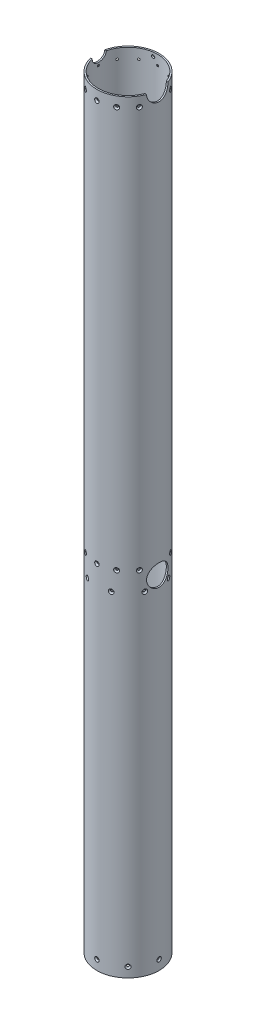
SolidWorks part; units mm, degrees
material "6063-T6"
ref_plane "Front Plane" through (0, 0, 0) normal (0, 0, 1) x (1, 0, 0)
ref_plane "Top Plane" through (0, 0, 0) normal (0, 1, 0) x (1, 0, 0)
ref_plane "Right Plane" through (0, 0, 0) normal (1, 0, 0) x (0, 0, -1)
sketch "Sketch1" plane through (0, 0, 0) normal (0, 1, 0) x (1, 0, 0)
  circle A0 centre (0, 0) radius 24.1554
  circle A1 centre (0, 0) radius 25.4
  dimension "D1" = 50.8
  dimension "D2" = 1.2446
extrude "body" add sketch "Sketch1" along normal blind 622.3
hole_wizard "M2x0.4 Tapped Hole1" positions "3DSketch1" profile "Sketch2" tap size "M2x0.4" standard "ANSI Metric"
sketch3d "3DSketch1"
  line L0 (25.4, 7.9375, 0) -> (-1.0246, 7.9375, 0)
  point P0 (25.4, 7.9375, 0)
sketch "Sketch2" plane through (25.4, 7.9375, 0) normal (0, 1, 0) x (0, 0, -1)
  line L0 (0, 0) -> (0, 8.3547)
  line L1 (0, 8.3547) -> (0.8, 7.874)
  line L2 (0.8, 7.874) -> (0.8, 1.09)
  line L3 (0.8, 1.09) -> (1.89, 0)
  line L4 (1.89, 0) -> (0, 0)
  line L5 (-0.8, 1.09) -> (-1.89, 0) construction
  line L6 (0, 8.3547) -> (-0.8, 7.874) construction
  line L7 (0, -6.35) -> (0, 107.95) construction
  dimension "Tap Drill Dia." = 1.6
  dimension "Tap Drill Depth" = 7.874
  dimension "Near C'Sink Dia." = 3.78
  dimension "Near C'Sink Angle" = 90
  dimension "Drill Angle" = 118
cosmetic thread "Hole Thread1"
pattern_circular "CirPattern1" count 8 over 360 about axis through (0, 0, 0) along (0, 1, 0) of "M2x0.4 Tapped Hole1"
cosmetic thread "Hole Thread2"
cosmetic thread "Hole Thread3"
cosmetic thread "Hole Thread4"
cosmetic thread "Hole Thread5"
cosmetic thread "Hole Thread6"
cosmetic thread "Hole Thread7"
cosmetic thread "Hole Thread8"
hole_wizard "M2x0.4 Tapped Hole2" positions "3DSketch2" profile "Sketch3" tap size "M2x0.4" standard "ANSI Metric"
sketch3d "3DSketch2"
  line L0 (23.4665, 271.4625, 9.7202) -> (2.1339, 271.4625, 0.8839)
  point P0 (23.4665, 271.4625, 9.7202)
sketch "Sketch3" plane through (23.4665, 271.4625, 9.7202) normal (0, 1, 0) x (0.3827, 0, -0.9239)
  line L0 (0, 0) -> (0, 8.3547)
  line L1 (0, 8.3547) -> (0.8, 7.874)
  line L2 (0.8, 7.874) -> (0.8, 1.09)
  line L3 (0.8, 1.09) -> (1.89, 0)
  line L4 (1.89, 0) -> (0, 0)
  line L5 (-0.8, 1.09) -> (-1.89, 0) construction
  line L6 (0, 8.3547) -> (-0.8, 7.874) construction
  line L7 (0, -6.35) -> (0, 107.95) construction
  dimension "Tap Drill Dia." = 1.6
  dimension "Tap Drill Depth" = 7.874
  dimension "Near C'Sink Dia." = 3.78
  dimension "Near C'Sink Angle" = 90
  dimension "Drill Angle" = 118
cosmetic thread "Hole Thread9"
pattern_circular "CirPattern2" count 8 over 360 about axis through (0, 622.3, 0) along (0, -1, 0) of "M2x0.4 Tapped Hole2" reverse direction yes
cosmetic thread "Hole Thread10"
cosmetic thread "Hole Thread11"
cosmetic thread "Hole Thread12"
cosmetic thread "Hole Thread13"
cosmetic thread "Hole Thread14"
cosmetic thread "Hole Thread15"
cosmetic thread "Hole Thread16"
hole_wizard "M2x0.4 Tapped Hole3" positions "3DSketch3" profile "Sketch4" tap size "M2x0.4" standard "ANSI Metric"
sketch3d "3DSketch3"
  line L0 (0, 614.3498, 25.4) -> (0, 614.3498, 15.3774)
  point P0 (0, 614.3498, 25.4)
sketch "Sketch4" plane through (0, 614.3498, 25.4) normal (1, 0, 0) x (0, -1, 0)
  line L0 (0, 0) -> (0, 8.3547)
  line L1 (0, 8.3547) -> (0.8, 7.874)
  line L2 (0.8, 7.874) -> (0.8, 1.09)
  line L3 (0.8, 1.09) -> (1.89, 0)
  line L4 (1.89, 0) -> (0, 0)
  line L5 (-0.8, 1.09) -> (-1.89, 0) construction
  line L6 (0, 8.3547) -> (-0.8, 7.874) construction
  line L7 (0, -6.35) -> (0, 107.95) construction
  dimension "Tap Drill Dia." = 1.6
  dimension "Tap Drill Depth" = 7.874
  dimension "Near C'Sink Dia." = 3.78
  dimension "Near C'Sink Angle" = 90
  dimension "Drill Angle" = 118
cosmetic thread "Hole Thread17"
pattern_circular "CirPattern3" count 12 over 360 about axis through (0, 622.3, 0) along (0, -1, 0) skipping 9 of "M2x0.4 Tapped Hole3"
cosmetic thread "Hole Thread18"
cosmetic thread "Hole Thread19"
cosmetic thread "Hole Thread20"
cosmetic thread "Hole Thread21"
cosmetic thread "Hole Thread22"
cosmetic thread "Hole Thread23"
cosmetic thread "Hole Thread24"
cosmetic thread "Hole Thread25"
cosmetic thread "Hole Thread26"
cosmetic thread "Hole Thread27"
hole_wizard "M2x0.4 Tapped Hole4" positions "3DSketch4" profile "Sketch5" tap size "M2x0.4" standard "ANSI Metric"
sketch3d "3DSketch4"
  line L0 (-25.4, 287.3502, 0) -> (-18.8369, 287.3502, 0)
  point P0 (-25.4, 287.3502, 0)
sketch "Sketch5" plane through (-25.4, 287.3502, 0) normal (0, 1, 0) x (0, 0, 1)
  line L0 (0, 0) -> (0, 8.3547)
  line L1 (0, 8.3547) -> (0.8, 7.874)
  line L2 (0.8, 7.874) -> (0.8, 1.09)
  line L3 (0.8, 1.09) -> (1.89, 0)
  line L4 (1.89, 0) -> (0, 0)
  line L5 (-0.8, 1.09) -> (-1.89, 0) construction
  line L6 (0, 8.3547) -> (-0.8, 7.874) construction
  line L7 (0, -6.35) -> (0, 107.95) construction
  dimension "Tap Drill Dia." = 1.6
  dimension "Tap Drill Depth" = 7.874
  dimension "Near C'Sink Dia." = 3.78
  dimension "Near C'Sink Angle" = 90
  dimension "Drill Angle" = 118
cosmetic thread "Hole Thread28"
pattern_circular "CirPattern4" count 12 over 360 about axis through (0, 622.3, 0) along (0, -1, 0) skipping 6 of "M2x0.4 Tapped Hole4" reverse direction yes
cosmetic thread "Hole Thread29"
cosmetic thread "Hole Thread30"
cosmetic thread "Hole Thread31"
cosmetic thread "Hole Thread32"
cosmetic thread "Hole Thread33"
cosmetic thread "Hole Thread34"
cosmetic thread "Hole Thread35"
cosmetic thread "Hole Thread36"
cosmetic thread "Hole Thread37"
cosmetic thread "Hole Thread38"
hole_wizard "43/64 (0.67188) Diameter Hole1" positions "3DSketch5" profile "Sketch6" hole size "11/16" standard "ANSI Inch"
sketch3d "3DSketch5"
  line L0 (25.4, 279.4, 0) -> (13.4323, 279.4, 0)
  point P0 (25.4, 279.4, 0)
  point P5 (25.4, 622.3, 0)
sketch "Sketch6" plane through (25.4, 279.4, 0) normal (0, 1, 0) x (0, 0, -1)
  line L0 (0, 0) -> (0, 33.9483)
  line L1 (0, 33.9483) -> (8.7312, 28.702)
  line L2 (8.7312, 28.702) -> (8.7312, 0)
  line L3 (8.7312, 0) -> (0, 0)
  line L4 (0, 33.9483) -> (-8.7313, 28.702) construction
  line L5 (0, -6.35) -> (0, 107.95) construction
  dimension "Hole Dia." = 17.4625
  dimension "Hole Depth" = 28.702
  dimension "Drill Angle" = 118
pattern_linear "LPattern1" [suppressed] of bodies 110
hole_wizard "7/16 Clearance Hole1" positions "3DSketch6" profile "Sketch7" hole size "7/16" standard "ANSI Inch"
sketch3d "3DSketch6"
  line L0 (-25.4, 279.4, 0) -> (-8.764, 279.4, 0)
  point P0 (-25.4, 279.4, 0)
  point P15 (-25.4, 622.3, 0)
sketch "Sketch7" plane through (-25.4, 279.4, 0) normal (0, 1, 0) x (0, 0, 1)
  line L0 (0, 0) -> (0, 32.1596)
  line L1 (0, 32.1596) -> (5.7544, 28.702)
  line L2 (5.7544, 28.702) -> (5.7544, 0)
  line L3 (5.7544, 0) -> (0, 0)
  line L4 (0, 32.1596) -> (-5.7544, 28.702) construction
  line L5 (0, -6.35) -> (0, 107.95) construction
  dimension "Hole Dia." = 11.5087
  dimension "Hole Depth" = 28.702
  dimension "Drill Angle" = 118
hole_wizard "3/32 (0.09375) Diameter Hole1" positions "Sketch8" profile "Sketch9" hole size "3/32" standard "ANSI Inch"
sketch "Sketch8" plane through (0, 0, -25.4) normal (0, 0, -1) x (-1, 0, 0)
  point P0 (3.4131, 619.125)
sketch "Sketch9" plane through (-3.4131, 619.125, -25.4) normal (1, 0, 0) x (0, 1, 0)
  line L0 (0, 0) -> (0, 30.6795)
  line L1 (0, 30.6795) -> (1.1906, 29.9641)
  line L2 (1.1906, 29.9641) -> (1.1906, 0)
  line L3 (1.1906, 0) -> (0, 0)
  line L4 (0, 30.6795) -> (-1.1906, 29.9641) construction
  line L5 (0, -6.35) -> (0, 107.95) construction
  dimension "Hole Dia." = 2.3812
  dimension "Hole Depth" = 29.9641
  dimension "Drill Angle" = 118
